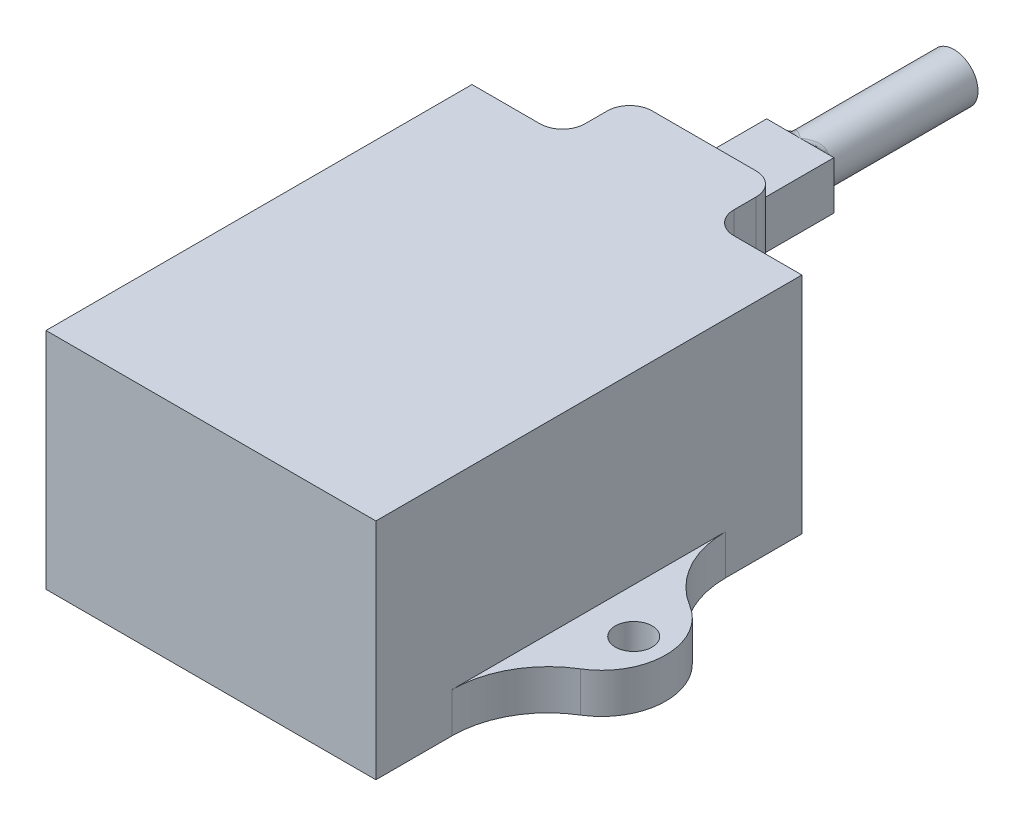
SolidWorks part; units mm, degrees
ref_plane "Front Plane" through (0, 0, 0) normal (0, 0, 1) x (1, 0, 0)
ref_plane "Top Plane" through (0, 0, 0) normal (0, 1, 0) x (1, 0, 0)
ref_plane "Right Plane" through (0, 0, 0) normal (1, 0, 0) x (0, 0, -1)
sketch "Sketch1" plane through (0, 0, 0) normal (0, 1, 0) x (1, 0, 0)
  line L1 (-13.081, 16.891) -> (13.081, 16.891)
  line L2 (-13.081, 16.891) -> (-13.081, -16.891)
  line L3 (-13.081, -16.891) -> (13.081, -16.891)
  line L4 (13.081, 16.891) -> (13.081, -16.891)
  line L5 (-13.081, 16.891) -> (13.081, -16.891) construction
  line L6 (-13.081, -16.891) -> (13.081, 16.891) construction
  point P0 (0, 0)
  dimension "D1" = 33.782
  dimension "D2" = 26.162
extrude "Boss-Extrude1" add sketch "Sketch1" along normal blind 17.78
sketch "Sketch2" plane through (0, 0, 0) normal (0, -1, 0) x (1, 0, 0)
  line L0 (0, 0) -> (0, 50000) construction
  line L1 (-19.177, 0) -> (19.177, 0) construction
  line L2 (-13.081, 16.891) -> (13.081, 16.891) construction
  circle A0 centre (16.637, 0) radius 1.4605
  circle A1 centre (14.097, 0) radius 5.08
  circle A2 centre (-16.637, 0) radius 1.4605
  circle A3 centre (-14.097, 0) radius 5.08
  dimension "D1" = 2.921
  dimension "D3" = 10.16
  dimension "D2" = 33.274
  dimension "D4" = 38.354
  dimension "D5" = 16.891
extrude "Boss-Extrude2" add sketch "Sketch2" against normal blind 3.175
fillet "Fillet1" radius 7.62 4 edges at (13.081, 1.5875, -4.9774) (13.081, 1.5875, 4.9774) (-13.081, 1.5875, 4.9774) (-13.081, 1.5875, -4.9774)
sketch "Sketch3" plane through (0, 0, -16.891) normal (0, 0, -1) x (-1, 0, 0)
  line L0 (-13.081, 17.78) -> (13.081, 17.78) construction
  line L1 (-5.9055, 5.969) -> (5.9055, 5.969)
  line L2 (-5.9055, 5.969) -> (-5.9055, 17.78)
  line L3 (-5.9055, 17.78) -> (5.9055, 17.78)
  line L4 (5.9055, 5.969) -> (5.9055, 17.78)
  line L5 (-5.9055, 5.969) -> (5.9055, 17.78) construction
  line L6 (-5.9055, 17.78) -> (5.9055, 5.969) construction
  point P0 (0, 11.8745)
  dimension "D1" = 11.811
  dimension "D2" = 11.811
extrude "Boss-Extrude3" add sketch "Sketch3" along normal blind 5.334
fillet "Fillet2" radius 1.778 4 edges at (-5.9055, 11.8745, -22.225) (5.9055, 11.8745, -22.225)
sketch "Sketch4" plane through (0, 0, -22.225) normal (0, 0, -1) x (-1, 0, 0)
  line L1 (2.667, 10.3453) -> (-2.667, 10.3453)
  line L2 (2.667, 10.3453) -> (2.667, 14.1553)
  line L3 (2.667, 14.1553) -> (-2.667, 14.1553)
  line L4 (-2.667, 10.3453) -> (-2.667, 14.1553)
  line L5 (2.667, 10.3453) -> (-2.667, 14.1553) construction
  line L6 (2.667, 14.1553) -> (-2.667, 10.3453) construction
  point P0 (0, 12.2503)
  dimension "D1" = 3.81
  dimension "D2" = 5.334
extrude "Boss-Extrude4" add sketch "Sketch4" along normal blind 7.62
sketch "Sketch5" plane through (0, 0, -29.845) normal (0, 0, -1) x (-1, 0, 0)
  line L0 (-2.667, 14.1553) -> (2.667, 10.3453) construction
  line L1 (2.667, 14.1553) -> (-2.667, 14.1553) construction
  circle A0 centre (0, 12.2503) radius 1.905
extrude "Boss-Extrude5" add sketch "Sketch5" along normal blind 12.192
fillet "Fillet3" radius 0.762 2 edges at (-1.905, 12.2503, -29.845) (1.905, 12.2503, -29.845)
